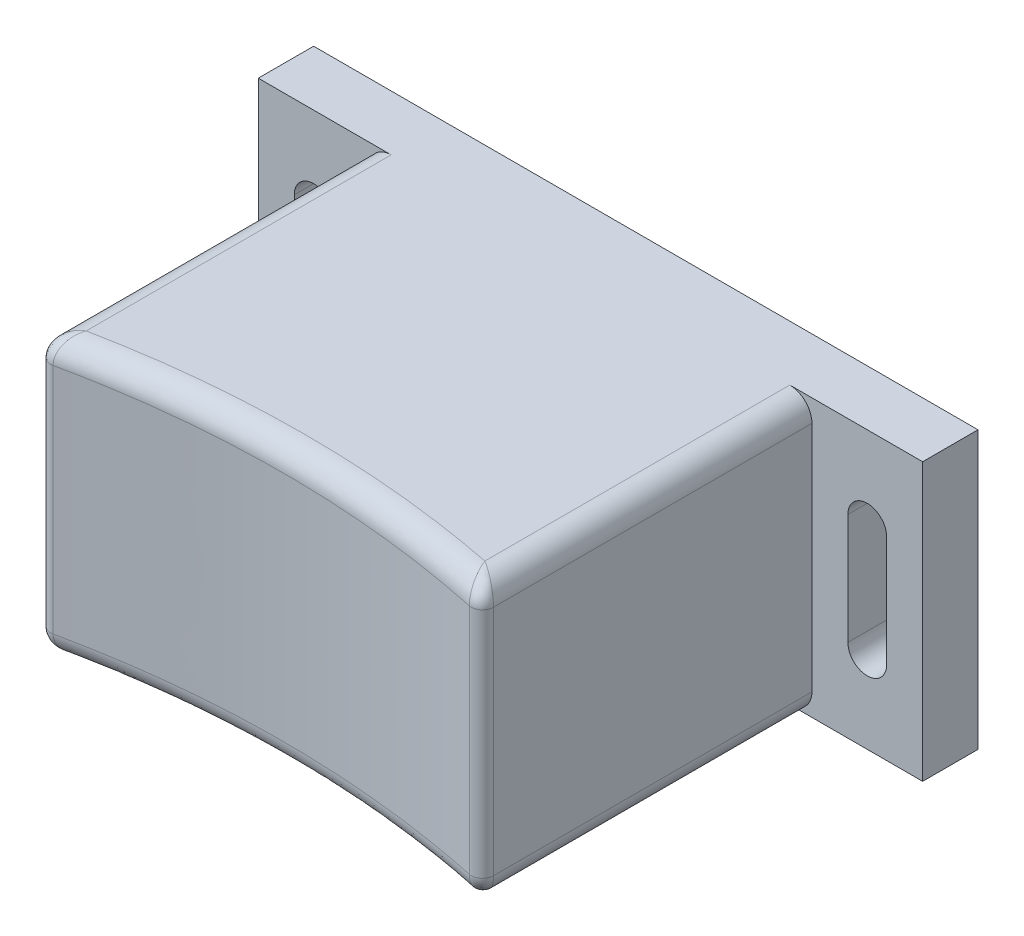
SolidWorks part; units mm, degrees
ref_plane "Front Plane" through (0, 0, 0) normal (0, 0, 1) x (1, 0, 0)
ref_plane "Top Plane" through (0, 0, 0) normal (0, 1, 0) x (1, 0, 0)
ref_plane "Right Plane" through (0, 0, 0) normal (1, 0, 0) x (0, 0, -1)
sketch "Sketch1" plane through (0, 0, 0) normal (0, 0, 1) x (1, 0, 0)
  line L1 (0, 0) -> (101.6, 0)
  line L2 (0, 0) -> (0, 63.5)
  line L3 (0, 63.5) -> (101.6, 63.5)
  line L4 (101.6, 0) -> (101.6, 63.5)
  dimension "D1" = 101.6
  dimension "D2" = 63.5
extrude "Boss-Extrude1" add sketch "Sketch1" along normal blind 88.9
sketch "Sketch2" plane through (0, 0, 88.9) normal (0, 0, 1) x (1, 0, 0)
  line L0 (0, 31.75) -> (101.6, 31.75) construction
  line L1 (0, 63.5) -> (0, 0) construction
  line L2 (101.6, 0) -> (101.6, 63.5) construction
  line L4 (50.8, 40.9154) -> (42.8625, 36.3327)
  line L5 (42.8625, 36.3327) -> (42.8625, 27.1673)
  line L6 (42.8625, 27.1673) -> (50.8, 22.5846)
  line L7 (50.8, 22.5846) -> (58.7375, 27.1673)
  line L8 (58.7375, 27.1673) -> (58.7375, 36.3327)
  line L9 (58.7375, 36.3327) -> (50.8, 40.9154)
  line L13 (0, 63.5) -> (0, 0)
  line L14 (0, 0) -> (101.6, 0)
  line L15 (101.6, 0) -> (101.6, 63.5)
  line L16 (101.6, 63.5) -> (0, 63.5)
  line L17 (0, 63.5) -> (0, 0)
  line L18 (0, 0) -> (101.6, 0)
  line L19 (101.6, 0) -> (101.6, 63.5)
  line L20 (101.6, 63.5) -> (0, 63.5)
  circle A0 centre (50.8, 31.75) radius 7.9375 construction
  line M7 (0, 63.5) -> (0, 0)
  line M8 (0, 0) -> (101.6, 0)
  line M9 (101.6, 0) -> (101.6, 63.5)
  line M10 (101.6, 63.5) -> (0, 63.5)
  dimension "D1" = 15.875
  dimension "D2" = 0
extrude "Cut-Extrude1" [suppressed] cut sketch "Sketch2" against normal blind 25.4 contours L9 L8 L7 L6 L5 L4 M10 M7 M8 M9
fillet "Fillet1" [suppressed] radius 6.35
fillet "Fillet2" [suppressed] radius 6.35
sketch "Sketch3" plane through (0, 0, 0) normal (0, 0, -1) x (-1, 0, 0)
  line L0 (-101.6, 0) -> (-101.6, 63.5) construction
  line L1 (-101.6, 0) -> (-127, 0)
  line L2 (-101.6, 0) -> (-101.6, 63.5)
  line L3 (-101.6, 63.5) -> (-127, 63.5)
  line L4 (-127, 0) -> (-127, 63.5)
  line L5 (0, 0) -> (-101.6, 0) construction
  line L6 (-114.3, 0) -> (-114.3, 63.5) construction
  line L7 (0, 0) -> (25.4, 0)
  line L8 (0, 0) -> (0, 63.5)
  line L9 (0, 63.5) -> (25.4, 63.5)
  line L10 (25.4, 0) -> (25.4, 63.5)
  line L11 (-114.3, 19.05) -> (-114.3, 44.45) construction
  line L12 (-118.745, 19.05) -> (-118.745, 44.45)
  line L13 (-109.855, 19.05) -> (-109.855, 44.45)
  line L14 (-50.8, 0) -> (-50.8, 63.5) construction
  line L15 (-101.6, 63.5) -> (0, 63.5) construction
  line L16 (12.7, 19.05) -> (12.7, 44.45) construction
  line L17 (17.145, 19.05) -> (17.145, 44.45)
  line L18 (8.255, 19.05) -> (8.255, 44.45)
  line L19 (0, 63.5) -> (-101.6, 63.5) construction
  arc A0 (-118.745, 19.05) -> (-109.855, 19.05) centre (-114.3, 19.05) ccw
  arc A1 (-109.855, 44.45) -> (-118.745, 44.45) centre (-114.3, 44.45) ccw
  arc A2 (17.145, 19.05) -> (8.255, 19.05) centre (12.7, 19.05) cw
  arc A3 (8.255, 44.45) -> (17.145, 44.45) centre (12.7, 44.45) cw
  point P17 (-114.3, 31.75)
  point P28 (12.7, 31.75)
  point P33 (0, 0)
  dimension "D2" = 4.445
  dimension "D1" = 25.4
  dimension "D3" = 25.4
extrude "Boss-Extrude2" add sketch "Sketch3" against normal blind 12.7
sketch "Sketch4" plane through (0, 63.5, 0) normal (0, 1, 0) x (1, 0, 0)
  line L0 (50.8, -88.9) -> (50.8, 0) construction
  line L1 (101.6, -88.9) -> (0, -88.9) construction
  line L2 (0, 0) -> (101.6, 0) construction
  line L3 (101.6, -88.9) -> (0, -88.9)
  spline S0 degree 2 poles (101.6, -88.9) (50.8, -77.489) (0, -88.9) knots 0 0 0 1 1 1
  point P8 (50.8, -92.5578)
  point P10 (50.8, -83.1945)
extrude "Cut-Extrude2" cut sketch "Sketch4" against normal through all
fillet "Fillet4" radius 2.54 2 edges at (0, 31.75, 88.9) (101.6, 31.75, 88.9)
fillet "Fillet5" radius 5.08 10 edges at (101.6, 0, 49.2236) (100.6599, 0, 87.72) (0, 0, 49.2236) (0.9401, 0, 87.72) (101.6, 63.5, 49.2236) (100.6599, 63.5, 87.72) (0, 63.5, 49.2236) (0.9401, 63.5, 87.72)
